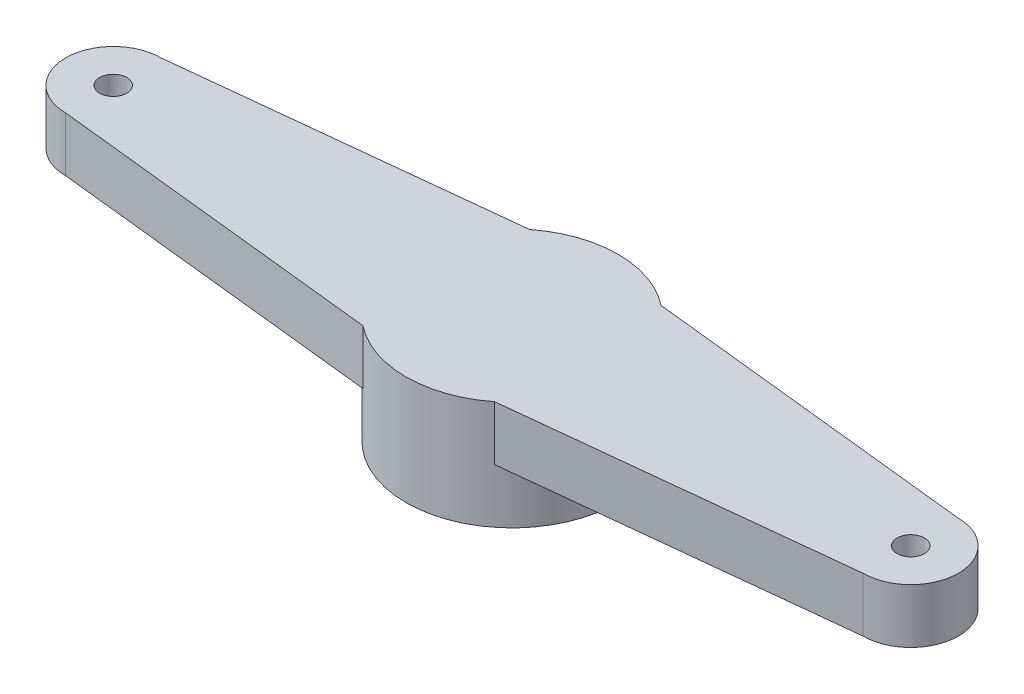
SolidWorks part; units mm, degrees
ref_plane "Front Plane" through (0, 0, 0) normal (0, 0, 1) x (1, 0, 0)
ref_plane "Top Plane" through (0, 0, 0) normal (0, 1, 0) x (1, 0, 0)
ref_plane "Right Plane" through (0, 0, 0) normal (1, 0, 0) x (0, 0, -1)
sketch "Sketch3" plane through (0, 0, 0) normal (0, 1, 0) x (1, 0, 0)
  circle A0 centre (-5.7066, -37.4292) radius 3.9
sketch "Sketch4" plane through (0, 0, 0) normal (0, 1, 0) x (1, 0, 0)
  circle A0 centre (-5.7066, -37.4292) radius 2.25
sketch "Sketch5" plane through (0, 0, 0) normal (0, 1, 0) x (1, 0, 0)
  line L0 (-5.7066, -50.2624) -> (-5.7066, -25.1139) construction
  line L1 (8.9434, -35.6792) -> (-5.7066, -34.109)
  line L2 (19.0383, -37.4292) -> (-31.5244, -37.4292) construction
  line L3 (8.9434, -39.1792) -> (-5.7066, -40.7493)
  line L4 (-20.3566, -35.6792) -> (-5.7066, -34.109)
  line L5 (-20.3566, -39.1792) -> (-5.7066, -40.7493)
  arc A0 (8.9434, -35.6792) -> (8.9434, -39.1792) centre (8.9434, -37.4292) cw
  circle A1 centre (8.9434, -37.4292) radius 0.5
  circle A2 centre (-20.3566, -37.4292) radius 0.5
  arc A3 (-20.3566, -35.6792) -> (-20.3566, -39.1792) centre (-20.3566, -37.4292) ccw
  point P15 (8.9434, -37.4292)
extrude "Boss-Extrude1" add sketch "Sketch3" along normal blind 2 and the other way blind 2 contours A0
extrude "Boss-Extrude4" add sketch "Sketch5" along normal blind 2
extrude "Cut-Extrude1" cut sketch "Sketch4" against normal through all
sketch "Sketch6" plane through (0, 0, 0) normal (0, 1, 0) x (1, 0, 0)
  point P0 (-20.3566, -37.4292)
  point P1 (8.9434, -37.4292)
sketch "Sketch7" plane through (0, 2, 0) normal (0, 1, 0) x (1, 0, 0)
  line L0 (-20.3566, -37.4292) -> (8.9434, -37.4292) construction
